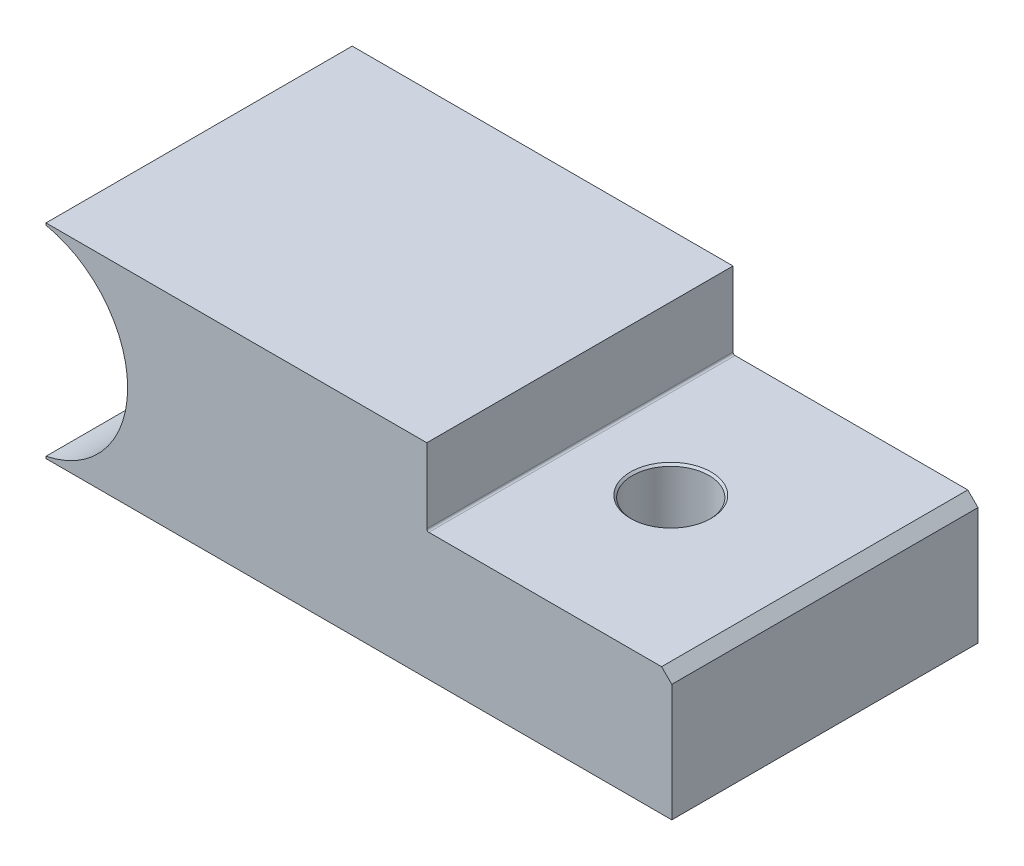
SolidWorks part; units mm, degrees
material "AISI Type A2 Tool Steel Custom"
ref_plane "Front Plane" through (0, 0, 0) normal (0, 0, 1) x (1, 0, 0)
ref_plane "Top Plane" through (0, 0, 0) normal (0, 1, 0) x (1, 0, 0)
ref_plane "Right Plane" through (0, 0, 0) normal (1, 0, 0) x (0, 0, -1)
sketch "Sketch1" plane through (0, 0, 0) normal (0, 0, 1) x (1, 0, 0)
  line L1 (2.54, 0) -> (80.4026, 0)
  line L3 (2.54, 25.4) -> (49.9226, 25.4)
  line L4 (80.4026, 0) -> (80.4026, 15.875)
  line L5 (2.54, 25.4) -> (2.54, 25.1434)
  line L6 (49.9226, 25.4) -> (49.9226, 15.875)
  line L7 (49.9226, 15.875) -> (80.4026, 15.875)
  line L8 (2.54, 0.2566) -> (2.54, 0)
  arc A1 (2.54, 0.2566) -> (2.54, 25.1434) centre (0, 12.7) ccw
  dimension "D2" = 25.4
  dimension "D1" = 47.3826
  dimension "D3" = 9.525
  dimension "D4" = 2.54
  dimension "D5" = 30.48
  dimension "D6" = 15.875
  dimension "D7" = 0.2566
extrude "Boss-Extrude1" add sketch "Sketch1" along normal blind 38.1
sketch "Sketch2" plane through (0, 15.875, 0) normal (0, 1, 0) x (1, 0, 0)
  line L1 (2.54, -38.1) -> (2.54, 0) construction
  point P0 (61.2257, -19.05)
  point P8 (2.54, -19.05)
  dimension "D1" = 58.6857
hole_wizard "3/8 (0.375) Diameter Hole1" positions "Sketch2" profile "Sketch4" hole size "3/8" standard "ANSI Inch" end condition through all
sketch "Sketch4" plane through (61.2257, 15.875, 19.05) normal (1, 0, 0) x (0, 0, 1)
  line L0 (0, 0) -> (0, 15.875)
  line L1 (0, 15.875) -> (4.7625, 15.875)
  line L2 (4.7625, 15.875) -> (4.7625, 0)
  line L5 (4.7625, 0) -> (0, 0)
  line L11 (0, -6.35) -> (0, 107.95) construction
  dimension "Thru Hole Dia." = 9.525
  dimension "Thru Hole Depth" = 15.875
chamfer "Chamfer1" distance 1.27 angle 45 1 edges at (80.4026, 15.875, 19.05)
chamfer "Chamfer2" distance 0.254 angle 45 1 edges at (61.2257, 15.875, 23.8125)
fillet "Fillet1" radius 0.254 1 edges at (49.9226, 15.875, 19.05)
